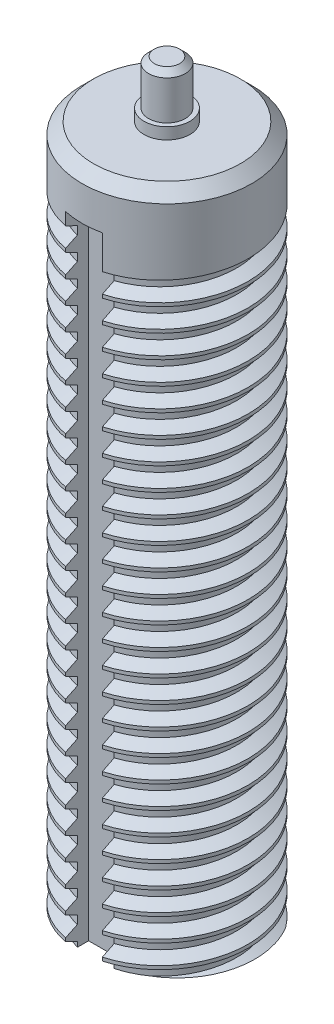
SolidWorks part; units mm, degrees
ref_plane "Front" through (0, 0, 0) normal (0, 0, 1) x (1, 0, 0)
ref_plane "Top" through (0, 0, 0) normal (0, 1, 0) x (1, 0, 0)
ref_plane "Right" through (0, 0, 0) normal (1, 0, 0) x (0, 0, -1)
sketch "Sketch1" plane through (0, 0, 0) normal (0, 1, 0) x (1, 0, 0)
  line L0 (0, 7.7142) -> (0, 0) construction
  line L1 (0, 0) -> (-8.1657, 0) construction
  line L2 (-1.6, 7.225) -> (-1.6, 5.225)
  line L3 (-1.6, 5.225) -> (1.6, 5.225)
  line L4 (1.6, 5.225) -> (1.6, 7.225)
  line L5 (1.6, -5.225) -> (1.6, -7.225)
  line L6 (-1.6, -5.225) -> (1.6, -5.225)
  line L7 (-1.6, -7.225) -> (-1.6, -5.225)
  circle A0 centre (0, 0) radius 7.4 construction
  arc A1 (-1.6, 7.225) -> (-1.6, -7.225) centre (0, 0) ccw
  arc A2 (1.6, -7.225) -> (1.6, 7.225) centre (0, 0) ccw
  dimension "D1" = 1.6
extrude "Boss-Extrude1" add sketch "Sketch1" along normal blind 70
sketch "Sketch2" plane through (0, 70, 0) normal (0, 1, 0) x (1, 0, 0)
  circle A0 centre (0, 0) radius 7.4
extrude "Boss-Extrude2" add sketch "Sketch2" against normal blind 4
sketch "Sketch3" plane through (0, 70, 0) normal (0, 1, 0) x (1, 0, 0)
  circle A0 centre (0, 0) radius 2
extrude "Boss-Extrude3" add sketch "Sketch3" along normal blind 1
sketch "Sketch4" plane through (0, 71, 0) normal (0, 1, 0) x (1, 0, 0)
  circle A0 centre (0, 0) radius 1.6
extrude "Boss-Extrude4" add sketch "Sketch4" along normal blind 3.9
chamfer "Chamfer1" distance 0.5 angle 45 1 edges at (0, 74.9, 1.6)
chamfer "Chamfer2" distance 1 angle 45 1 edges at (0, 70, 7.4)
sketch "Sketch6" plane through (0, 0, 0) normal (1, 0, 0) x (0, 0, -1)
  line L0 (7.4, 0) -> (7.4, -1.7)
  line L5 (7.4, -1.7) -> (6.4, -1.2)
  line L6 (6.4, -1.2) -> (6.4, -0.5)
  line L7 (6.4, -0.5) -> (7.4, 0)
  line L9 (7.4, 69) -> (7.4, -41.0617) construction
  line L10 (-7.225, 0) -> (7.225, 0) construction
  point P0 (7.4, 0)
  dimension "D1" = 0.5
  dimension "D2" = 0.5
  dimension "D3" = 1
sketch "Sketch7" plane through (0, 0, 0) normal (0, -1, 0) x (1, 0, 0)
  circle A0 centre (0, 0) radius 7.4
curve "Helix/Spiral2" pitch 2 height 65 radius 7.4 centre (0, 0, 0) axis (0, 1, 0) start towards (0, 0, -1)
sweep "Cut-Sweep2" cut profiles "Sketch6" path "Helix/Spiral2" align with end faces yes
sketch "Sketch8" plane through (0, 0, 0) normal (0, 0, 1) x (1, 0, 0)
  line L0 (-16.0842, 10) -> (15.9837, 10)
  line L1 (15.9837, 10) -> (15.9837, -2.6663)
  line L2 (15.9837, -2.6663) -> (-16.0842, -2.6663)
  line L3 (-16.0842, -2.6663) -> (-16.0842, 10)
  dimension "D1" = 10
extrude "Cut-Extrude1" cut sketch "Sketch8" against normal through all both and the other way through all
